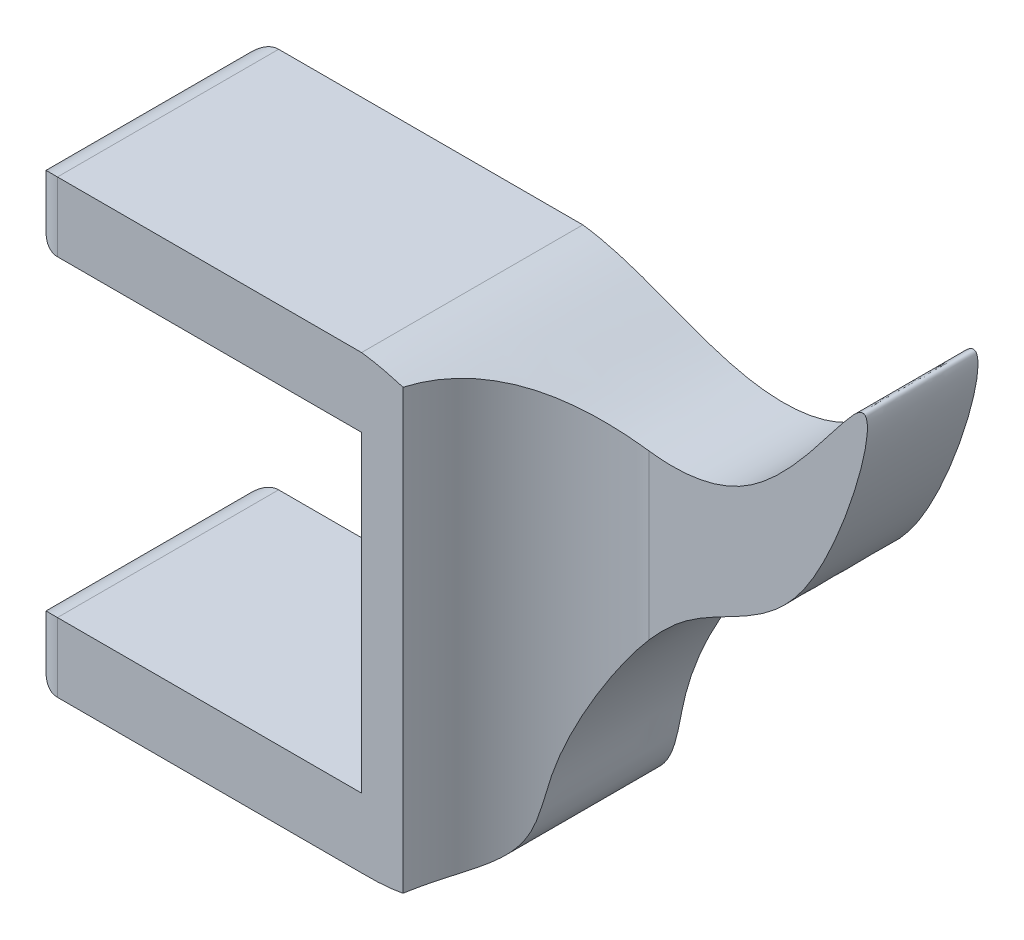
SolidWorks part; units mm, degrees
ref_plane "前视基准面" through (0, 0, 0) normal (0, 0, 1) x (1, 0, 0)
ref_plane "上视基准面" through (0, 0, 0) normal (0, 1, 0) x (1, 0, 0)
ref_plane "右视基准面" through (0, 0, 0) normal (1, 0, 0) x (0, 0, -1)
sketch "草图1" plane through (0, 0, 0) normal (0, 0, 1) x (1, 0, 0)
  line L0 (0, 0) -> (12, 0)
  line L1 (12, 0) -> (12, -11.3)
  line L3 (0, 0) -> (0, 2.5)
  line L4 (0, 2.5) -> (12, 2.5)
  line L6 (0, -13.8) -> (12, -13.8)
  line L7 (12, -11.3) -> (0, -11.3)
  line L8 (0, -11.3) -> (0, -13.8)
  spline S0 degree 3 poles (12, 2.5) (14.0892, 2.2294) (17.1584, 0.3025) (22.7398, 0.6379) (27.759, 9.3341) (24.4501, -2.7521) (19.3307, -3.0884) (14.9405, -10.3225) (15.4847, -13.8528) (12, -13.8) knots 0 0 0 0 0.1288 0.211965 0.331338 0.511511 0.671766 0.852724 1 1 1 1
  point P3 (0, 0)
  point P5 (14.9615, -10.5399)
  point P14 (18.325, -3.6489)
  point P16 (13.9771, -13.8214)
  point P18 (15.2896, -10.581)
  point P20 (17.8738, -4.5923)
  point P22 (14.2232, -13.6983)
  point P23 (15.6998, -10.4169)
  point P24 (14.3052, -13.8624)
  point P26 (17.5046, -5.0845)
  point P27 (18.407, -4.6333)
  point P28 (19.5965, -4.1411)
  point P29 (25.9954, 5.6212)
  point P30 (14.5394, -13.7022)
  point P31 (14.5107, -13.4551)
  point P32 (14.5758, -13.2449)
  dimension "D1" = 2.5
  dimension "D2" = 12
  dimension "D3" = 11.3
  dimension "D4" = 2.5
  dimension "D5" = 12
extrude "凸台-拉伸1" add sketch "草图1" along normal blind 8
sketch "草图3" plane through (0, -13.8, 0) normal (0, -1, 0) x (1, 0, 0)
  line L1 (27.5264, 4) -> (13.5, 4)
  line L2 (13.5, 4) -> (13.5, 8)
  line L4 (12, 8) -> (12, 0) construction
  line L9 (13.5, 8) -> (27.5264, 8)
  line L10 (27.5264, 8) -> (27.5264, 4)
  dimension "D1" = 1.5
extrude "切除-拉伸1" cut sketch "草图3" against normal blind 40
fillet "圆角8" radius 1 8 edges at (0, 0, 4) (0, 2.5, 4) (0, 1.25, 8) (0, 1.25, 0) (0, -11.3, 4) (0, -12.55, 8) (0, -13.8, 4) (0, -12.55, 0)
fillet "圆角11" radius 0.5 1 edges at (12, -5.65, 0)
fillet "圆角12" radius 5 1 edges at (13.5, -5.7613, 4)
